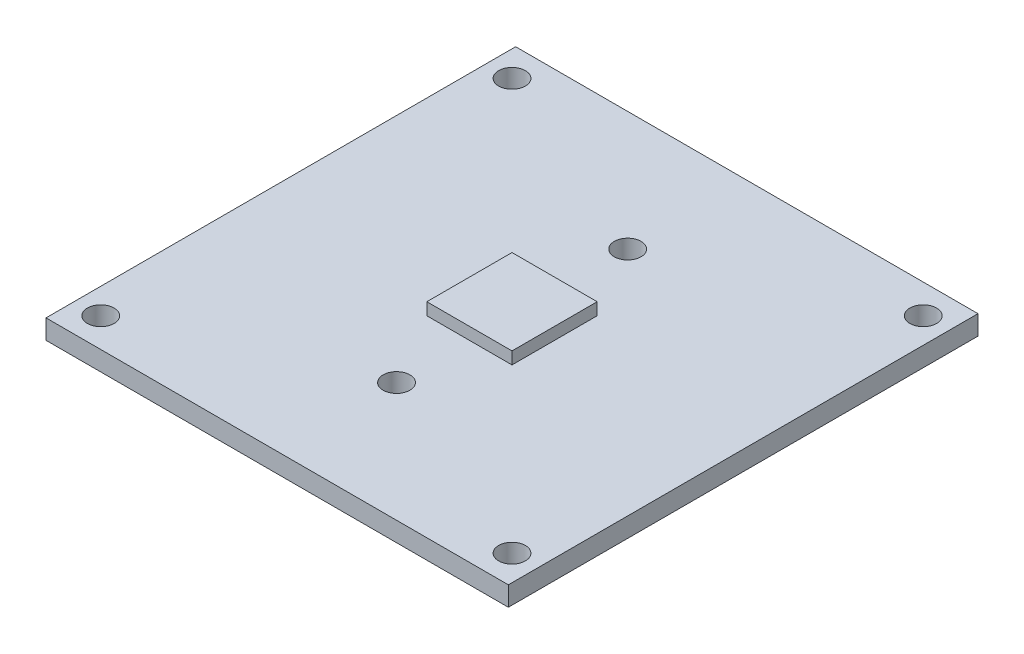
SolidWorks part; units mm, degrees
material "FR4_stuffedProtoboard"
ref_plane "Front Plane" through (0, 0, 0) normal (0, 0, 1) x (1, 0, 0)
ref_plane "Top Plane" through (0, 0, 0) normal (0, 1, 0) x (1, 0, 0)
ref_plane "Right Plane" through (0, 0, 0) normal (1, 0, 0) x (0, 0, -1)
sketch "Sketch1" plane through (0, 0, 0) normal (0, 1, 0) x (1, 0, 0)
  line L0 (-7.4919, 7.6) -> (-1.9919, 7.6)
  line L1 (-19, -19.3) -> (19, -19.3)
  line L2 (-19, -19.3) -> (-19, 19.3)
  line L3 (-19, 19.3) -> (19, 19.3)
  line L4 (19, -19.3) -> (19, 19.3)
  line L5 (-19, -19.3) -> (19, 19.3) construction
  line L6 (-19, 19.3) -> (19, -19.3) construction
  line L7 (2.0081, 9.5) -> (2.0081, 7.6)
  line L8 (-1.9919, 7.6) -> (-1.9919, 9.5)
  line L9 (-1.9919, -7.6) -> (-7.4919, -7.6)
  line L10 (-1.9919, -9.5) -> (-1.9919, -7.6)
  line L11 (2.0081, -7.6) -> (2.0081, -9.5)
  line L12 (7.5081, -7.6) -> (2.0081, -7.6)
  line L13 (7.5081, 7.6) -> (7.5081, -7.6)
  line L14 (2.0081, 7.6) -> (7.5081, 7.6)
  line L15 (-7.4919, -7.6) -> (-7.4919, 7.6)
  line L16 (-19, 0) -> (19, 0) construction
  line L17 (0, 19.3) -> (0, -19.3) construction
  line L19 (-16, -14.3) -> (16, -14.3)
  line L20 (-16, -14.3) -> (-16, 14.3)
  line L21 (-16, 14.3) -> (16, 14.3)
  line L22 (16, -14.3) -> (16, 14.3)
  line L23 (-16, -14.3) -> (16, 14.3) construction
  line L24 (-16, 14.3) -> (16, -14.3) construction
  line L25 (-3.5, -3.5) -> (3.5, -3.5)
  line L26 (-3.5, -3.5) -> (-3.5, 3.5)
  line L27 (-3.5, 3.5) -> (3.5, 3.5)
  line L28 (3.5, -3.5) -> (3.5, 3.5)
  line L29 (-3.5, -3.5) -> (3.5, 3.5) construction
  line L30 (-3.5, 3.5) -> (3.5, -3.5) construction
  arc A0 (2.0081, 9.5) -> (-1.9919, 9.5) centre (0.0081, 9.5) ccw
  arc A3 (-1.9919, -9.5) -> (2.0081, -9.5) centre (0.0081, -9.5) ccw
  circle A6 centre (0.0081, 9.5) radius 1.1
  circle A7 centre (0.0081, -9.5) radius 1.1
  circle A8 centre (-16.9, 16.9) radius 1.1
  circle A9 centre (16.9, 16.9) radius 1.1
  circle A10 centre (16.9, -16.9) radius 1.1
  circle A11 centre (-16.9, -16.9) radius 1.1
  circle A12 centre (0.0081, 9.5) radius 2
  circle A13 centre (0.0081, -9.5) radius 2
  point P0 (0, 0)
  point P34 (7.5081, 0)
  point P35 (-7.4919, 0)
  point P36 (0, 0)
  point P41 (0, 0)
  dimension "D3" = 2.2
  dimension "D6" = 2
  dimension "D7" = 2.2
  dimension "D8" = 2.4
  dimension "D9" = 2.1
  dimension "D1" = 38.6
  dimension "D2" = 38
  dimension "D4" = 15.2
  dimension "D5" = 15
  dimension "D10" = 11.5081
  dimension "D11" = 5.5
  dimension "D12" = 4
  dimension "D13" = 19
  dimension "D14" = 3
  dimension "D15" = 5
  dimension "D16" = 7
extrude "Camera Board Base" add sketch "Sketch1" along normal blind 1.6 contours L1 L4 L3 L2 A9 A8 L22 L19 L20 L21 A10 A11 | L19 L22 L21 L20 A3 L10 L9 L15 L0 L8 A0 L7 L14 L13 L12 L11 | L10 A3 L11 L12 L13 L14 L7 A0 L8 L0 L15 L9 A6 A7 | L25 L28 L27 L26 | A0 A12 A6 | A13 A3 A7 region at (-4.7419, 0, -7.3579) region at (0.0081, 0, -11.4434) region at (0.0081, 0, 7.5566) region at (-18.4583, 0, 0) region at (-15.5708, 0, 0) region at (0, 0, 0)
extrude "Components" add sketch "Sketch1<3>" against normal blind 2.3 contours L19 L22 L21 L20 A3 L10 L9 L15 L0 L8 A0 L7 L14 L13 L12 L11 | L10 A3 L11 L12 L13 L14 L7 A0 L8 L0 L15 L9 A6 A7 | L25 L28 L27 L26 region at (-4.7419, 0, -7.3579) region at (-15.5708, 0, 0) region at (0, 0, 0)
sketch "Sketch1<3>" plane through (0, 0, 0) normal (0, 1, 0) x (1, 0, 0) same geometry as "Sketch1"
ref_plane "Plane1" through (0, 1.6, 0) normal (0, 1, 0) x (1, 0, 0)
sketch "Sketch2" plane through (0, 1.6, 0) normal (0, 1, 0) x (1, 0, 0)
  line L1 (-3.5, -3.5) -> (3.5, -3.5)
  line L2 (-3.5, -3.5) -> (-3.5, 3.5)
  line L3 (-3.5, 3.5) -> (3.5, 3.5)
  line L4 (3.5, -3.5) -> (3.5, 3.5)
  line L5 (-3.5, -3.5) -> (3.5, 3.5) construction
  line L6 (-3.5, 3.5) -> (3.5, -3.5) construction
  point P0 (0, 0)
extrude "Sensor" add sketch "Sketch2" along normal blind 1
